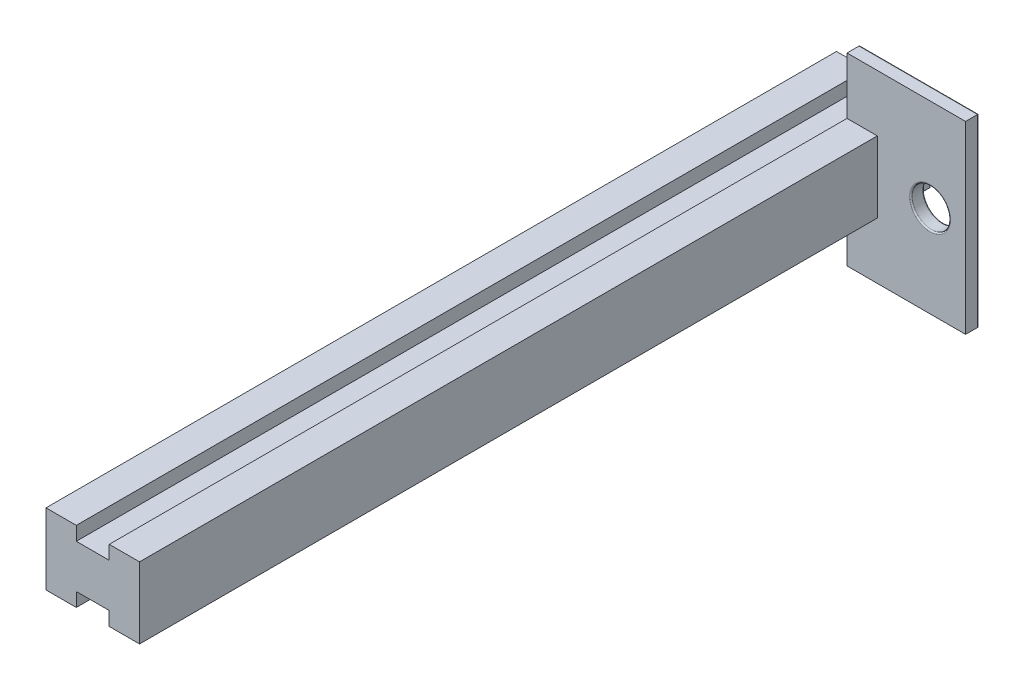
SolidWorks part; units mm, degrees
ref_plane "Front Plane" through (0, 0, 0) normal (0, 0, 1) x (1, 0, 0)
ref_plane "Top Plane" through (0, 0, 0) normal (0, 1, 0) x (1, 0, 0)
ref_plane "Right Plane" through (0, 0, 0) normal (1, 0, 0) x (0, 0, -1)
sketch "Sketch1" plane through (0, 0, 0) normal (0, 0, 1) x (1, 0, 0)
  line L8 (-1.3, 2.75) -> (-3.6, 2.75)
  line L9 (-1.3, 2.75) -> (-1.3, 1.7)
  line L10 (-1.3, -2.65) -> (-3.6, -2.65)
  line L11 (-3.6, 2.75) -> (-3.6, -2.65)
  line L14 (-1.3, -1.6) -> (-1.3, -2.65)
  line L15 (1.2, 2.75) -> (3.5, 2.75)
  line L16 (1.2, 2.75) -> (1.2, 1.7)
  line L17 (1.2, -2.65) -> (3.5, -2.65)
  line L18 (3.5, 2.75) -> (3.5, -2.65)
  line L21 (1.2, -1.6) -> (1.2, -2.65)
  line L22 (1.2, -1.6) -> (-1.3, -1.6)
  line L23 (1.2, 1.7) -> (-1.3, 1.7)
  point P0 (0, 0)
  dimension "D1" = 7.1
  dimension "D2" = 2.5
  dimension "D3" = 1.05
  dimension "D4" = 5.4
extrude "Boss-Extrude1" add sketch "Sketch1" along normal blind 60 contours L8 L11 L10 L14 L22 L21 L17 L18 L15 L16 L23 L9
sketch "Sketch2" plane through (0, 2.75, 0) normal (0, 1, 0) x (1, 0, 0)
  line L0 (2.35, 0) -> (2.35, -3) construction
  line L1 (1.2, 0) -> (3.5, 0) construction
  line L2 (1.2, -60) -> (1.2, 0) construction
  line L3 (1.2, -3) -> (3.5, -3)
  line L4 (3.5, -60) -> (3.5, 0) construction
  line L5 (3.5, -3) -> (3.5, -4)
  line L6 (3.5, -4) -> (1.2, -4)
  line L7 (1.2, -4) -> (1.2, -3)
  dimension "D1" = 3
  dimension "D2" = 1
extrude "Cut-Extrude1" cut sketch "Sketch2" against normal blind 10
sketch "Sketch3" plane through (1.2, 0, 0) normal (1, 0, 0) x (0, 0, -1)
  line L4 (0, 0) -> (-3, 0.05) construction
  line L5 (-3, -1.6) -> (-3, 1.7) construction
  line L6 (-3, 7.05) -> (-3, -6.95)
  line L7 (-3, -6.95) -> (-4, -6.95)
  line L8 (-4, -6.95) -> (-4, 7.05)
  line L9 (-4, 7.05) -> (-3, 7.05)
  point P9 (-3, 0.05)
  dimension "D1" = 1
  dimension "D2" = 14
extrude "Boss-Extrude2" add sketch "Sketch3" along normal blind 9
sketch "Sketch4" plane through (0, 0, 3) normal (0, 0, -1) x (-1, 0, 0)
  line L0 (0, 0) -> (-7.5, 0) construction
  circle A0 centre (-7.5, 0) radius 1.45
  dimension "D2" = 2.9
  dimension "D1" = 7.5
extrude "Cut-Extrude2" cut sketch "Sketch4" against normal blind 9
fillet "Fillet1" radius 0.1 12 edges at (1.2, -2.65, 1.5) (1.2, 2.75, 1.5) (3.5, 0.05, 3) (2.35, -2.65, 3) (5.7, -6.95, 3) (1.2, -4.8, 3) (2.35, 2.75, 3) (1.2, 4.9, 3) (5.7, 7.05, 3) (10.2, 0.05, 3) (6.05, 0, 4) (6.05, 0, 3)
